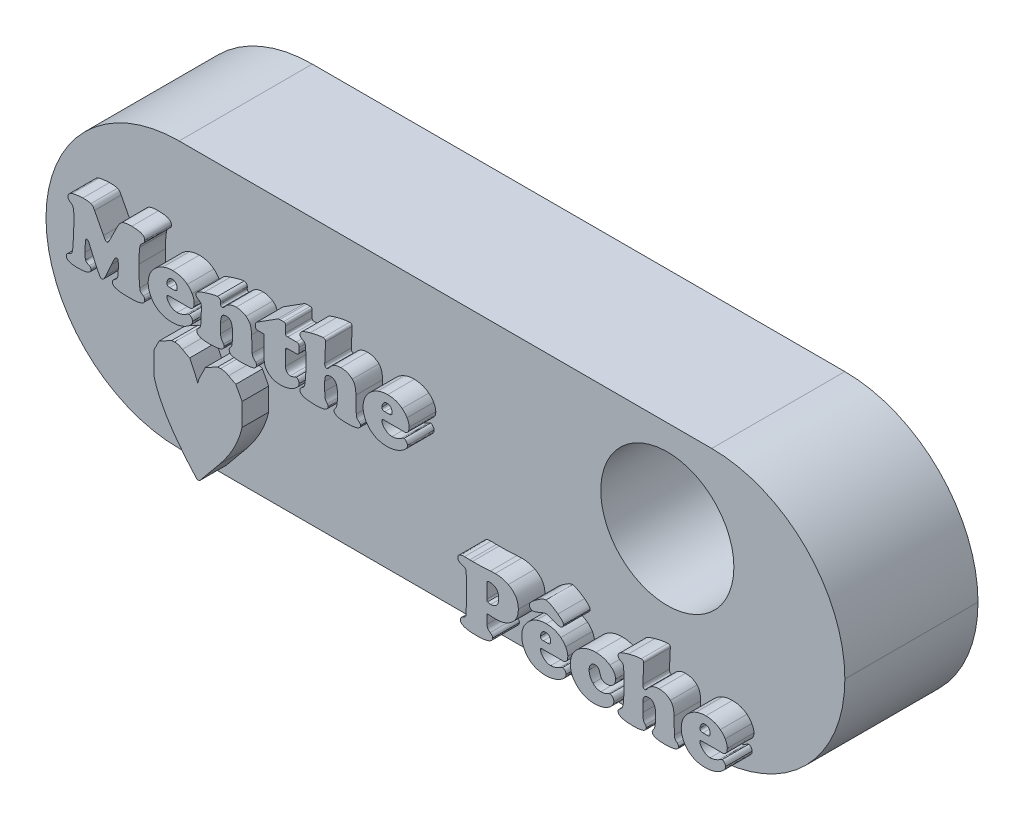
SolidWorks part; units mm, degrees
ref_plane "Plan de face" through (0, 0, 0) normal (0, 0, 1) x (1, 0, 0)
ref_plane "Plan de dessus" through (0, 0, 0) normal (0, 1, 0) x (1, 0, 0)
ref_plane "Plan de droite" through (0, 0, 0) normal (1, 0, 0) x (0, 0, -1)
sketch "Esquisse1" plane through (0, 0, 0) normal (0, 0, 1) x (1, 0, 0)
  line L1 (0, 0) -> (60, 0)
  line L2 (0, 0) -> (0, -20)
  line L3 (0, -20) -> (60, -20)
  line L4 (60, 0) -> (60, -20)
  dimension "D1" = 60
  dimension "D2" = 20
extrude "Boss.-Extru.1" add sketch "Esquisse1" along normal blind 10
fillet "Congé1" radius 10 4 edges at (60, -20, 5) (60, 0, 5) (0, -20, 5) (0, 0, 5)
sketch "Esquisse2" plane through (0, 0, 10) normal (0, 0, 1) x (1, 0, 0)
  text T0 "  Menthe\r\n                   Pêche" font "Cooper Black" height in points 20
extrude "Boss.-Extru.2" add sketch "Esquisse2" along normal blind 2
sketch "Esquisse4" plane through (0, 0, 0) normal (0, 0, 1) x (1, 0, 0)
  circle A0 centre (46.6655, -6.8878) radius 5
extrude "Enlèv. mat.-Extru.1" cut sketch "Esquisse4" along normal blind 10
sketch "Esquisse5" plane through (0, 0, 10) normal (0, 0, 1) x (1, 0, 0)
  text T0 "v" font "SWMap" height 3.5
extrude "Boss.-Extru.3" add sketch "Esquisse5" along normal blind 2
sketch "Esquisse6" plane through (0, 0, 10) normal (0, 0, 1) x (1, 0, 0)
  line L7 (12.4807, -12.1134) -> (11.8849, -11.8026)
  line L8 (10.9667, -12.1048) -> (10.6501, -12.7265)
  line L9 (10.6501, -12.7265) -> (10.6501, -14.1052)
  line L10 (16.1764, -14.2376) -> (16.1764, -12.7524)
  line L11 (16.1764, -12.7524) -> (15.8598, -12.1134)
  line L12 (15.8598, -12.1134) -> (15.2755, -11.8026)
  line L13 (13.6464, -13.9267) -> (13.5054, -14.0707)
  line L14 (12.4807, -12.1134) -> (11.8849, -11.8026)
  line L15 (10.9667, -12.1048) -> (10.6501, -12.7265)
  line L16 (10.6501, -12.7265) -> (10.6501, -14.1052)
  line L17 (16.1764, -14.2376) -> (16.1764, -12.7524)
  line L18 (16.1764, -12.7524) -> (15.8598, -12.1134)
  line L19 (15.8598, -12.1134) -> (15.2755, -11.8026)
  line L20 (13.6464, -13.9267) -> (13.5054, -14.0707)
  spline S14 degree 3 poles (3844.603, 1134.0387) (-9.1292, -38.311) (15.7913, -21.7573) (13.0686, -13.6013) (13.0014, -13.3955) (12.9149, -13.1747) (12.8254, -12.9335) (12.7197, -12.6762) (6.1298, 3.2524) (-24.1776, 9.0682) (3677.1074, 1590.1401) knots -12.728243 -12.728243 -12.728243 -12.728243 0.089256 0.188553 0.297501 0.417109 0.547777 0.687337 0.838518 26.665706 26.665706 26.665706 26.665706 only from (13.1802, -13.9642) to (12.4807, -12.1134)
  spline S15 degree 3 poles (587.959, 3946.2573) (12.648, -51.8598) (17.3042, 25.8245) (0.4195, -47.052) (568.98, 3949.021) knots -54.599144 -54.599144 -54.599144 -54.599144 0.529824 53.467941 53.467941 53.467941 53.467941 only from (11.8849, -11.8026) to (11.7093, -11.7767)
  spline S16 degree 3 poles (-1233.2066, 3789.2515) (37.5147, -63.203) (-8.3641, 47.0449) (23.9946, -79.0662) (-1258.6195, 3780.9629) knots -31.518562 -31.518562 -31.518562 -31.518562 0.435223 35.38032 35.38032 35.38032 35.38032 only from (11.7093, -11.7767) to (11.3323, -11.9091)
  spline S17 degree 3 poles (2009.0822, -3477.0911) (13.6411, 17.2413) (18.4038, -7.9741) (11.1107, -12.0374) (7.9091, -13.694) (-4.7846, 5.7961) (1645.5506, -3662.6786) knots -59.489645 -59.489645 -59.489645 -59.489645 0.354396 0.639968 0.857046 26.377837 26.377837 26.377837 26.377837 only from (11.3323, -11.9091) to (10.9667, -12.1048)
  spline S18 degree 3 poles (-3836.134, -1109.4642) (63.2387, 29.0811) (5.9159, -2.229) (11.0298, -15.3237) (18.91, -31.0876) (80.5387, -15.7714) (-3432.1342, -2050.4369) knots -14.844679 -14.844679 -14.844679 -14.844679 0.226693 0.467185 0.724557 19.777076 19.777076 19.777076 19.777076 only from (10.6501, -14.1052) to (11.7295, -16.5633)
  spline S19 degree 3 poles (-3268.2956, -2305.2844) (4.9825, 15.5644) (3.0038, -4.5004) (11.948, -16.8673) (12.1051, -17.0786) (12.3007, -17.3334) (12.5281, -17.6342) (12.7952, -17.9769) (33.9761, -45.6072) (72.3133, -59.8182) (-3088.6173, -2542.2179) knots -16.179282 -16.179282 -16.179282 -16.179282 0.053217 0.12705 0.222114 0.336151 0.472253 0.62734 0.803045 37.885684 37.885684 37.885684 37.885684 only from (11.7295, -16.5633) to (13.419, -18.7853)
  spline S20 degree 3 poles (3108.5675, -2551.7121) (-37.811, -35.1971) (-0.0046, -36.1208) (13.9989, -18.0518) (14.2513, -17.732) (14.4724, -17.4454) (14.6624, -17.1914) (14.8238, -16.9728) (21.4502, -7.8129) (9.6465, 14.1742) (3307.7145, -2287.4565) knots -24.739508 -24.739508 -24.739508 -24.739508 0.183136 0.349903 0.499297 0.632991 0.749514 0.849515 0.933004 13.230667 13.230667 13.230667 13.230667 only from (13.419, -18.7853) to (15.0683, -16.6266)
  spline S21 degree 3 poles (3430.9793, -2097.2443) (-52.7913, -15.306) (7.6962, -30.9989) (15.77, -15.4208) (21.2981, -2.0665) (-31.8036, 30.3158) (3828.6402, -1223.5898) knots -19.08667 -19.08667 -19.08667 -19.08667 0.27548 0.532761 0.773255 16.618162 16.618162 16.618162 16.618162 only from (15.0683, -16.6266) to (16.1764, -14.2376)
  spline S22 degree 3 poles (644.2769, 3938.291) (14.7565, -51.6748) (21.3639, 27.7582) (3.1353, -50.9536) (627.0794, 3940.8651) knots -50.617147 -50.617147 -50.617147 -50.617147 0.489777 52.311517 52.311517 52.311517 52.311517 only from (15.2755, -11.8026) to (15.1086, -11.7767)
  spline S23 degree 3 poles (-1203.2594, 3797.9802) (40.6365, -63.015) (-4.5108, 46.9654) (26.6781, -79.1301) (-1229.2734, 3789.5071) knots -31.580828 -31.580828 -31.580828 -31.580828 0.433634 35.522114 35.522114 35.522114 35.522114 only from (15.1086, -11.7767) to (14.7229, -11.9091)
  spline S24 degree 3 poles (-1803.9059, 3550.266) (52.9114, -2.5252) (31.2141, -2.5411) (14.4957, -12.0377) (10.845, -13.8855) (-0.8275, 1.8881) (1667.8389, -3653.483) knots -137.313568 -137.313568 -137.313568 -137.313568 0.364348 0.648317 0.864177 29.749606 29.749606 29.749606 29.749606 only from (14.7229, -11.9091) to (14.3545, -12.1048)
  spline S25 degree 3 poles (-3534.0211, 1833.631) (40.3586, -14.9997) (16.2434, -7.9177) (14.2522, -12.3115) (14.1882, -12.475) (14.1067, -12.6813) (14.0086, -12.9299) (13.8996, -13.2237) (5.8362, -35.9895) (-23.9616, -50.8213) (3751.9324, -1435.324) knots -7.190391 -7.190391 -7.190391 -7.190391 0.043456 0.109956 0.200409 0.312725 0.450185 0.610367 0.793303 37.494525 37.494525 37.494525 37.494525 only from (14.3545, -12.1048) to (13.6464, -13.9267)
  spline S26 degree 3 poles (843.9363, -3926.7955) (10.828, 15.7726) (19.9546, -45.548) (2.5294, 19.0599) (832.9813, -3928.9445) knots -60.477404 -60.477404 -60.477404 -60.477404 0.442775 66.294156 66.294156 66.294156 66.294156 only from (13.5054, -14.0707) to (13.419, -14.0879)
  spline S27 degree 3 poles (-1820.1277, -3568.9332) (49.1443, 42.8981) (-17.5601, -73.557) (39.1184, 47.987) (-1835.0835, -3561.1398) knots -30.851382 -30.851382 -30.851382 -30.851382 0.500538 31.829171 31.829171 31.829171 31.829171 only from (13.419, -14.0879) to (13.1802, -13.9642)
  spline S28 degree 3 poles (13.1802, -13.9642) (13.1643, -13.9074) (13.1308, -13.7876) (13.0686, -13.6013) (13.0014, -13.3955) (12.9149, -13.1747) (12.8254, -12.9335) (12.7197, -12.6762) (12.6056, -12.4004) (12.5232, -12.2111) (12.4807, -12.1134) knots 0 0 0 0 0.089256 0.188553 0.297501 0.417109 0.547777 0.687337 0.838518 1 1 1 1
  spline S29 degree 3 poles (11.8849, -11.8026) (11.8544, -11.7946) (11.7968, -11.7797) (11.7373, -11.7776) (11.7093, -11.7767) knots 0 0 0 0 0.529824 1 1 1 1
  spline S30 degree 3 poles (11.7093, -11.7767) (11.6507, -11.7839) (11.5159, -11.8005) (11.3985, -11.8699) (11.3323, -11.9091) knots 0 0 0 0 0.435223 1 1 1 1
  spline S31 degree 3 poles (11.3323, -11.9091) (11.2902, -11.9342) (11.2142, -11.9797) (11.1107, -12.0374) (11.0312, -12.0785) (10.9851, -12.0973) (10.9667, -12.1048) knots 0 0 0 0 0.354396 0.639968 0.857046 1 1 1 1
  spline S32 degree 3 poles (10.6501, -14.1052) (10.6964, -14.3042) (10.7918, -14.7143) (11.0298, -15.3237) (11.3415, -15.9472) (11.5973, -16.3533) (11.7295, -16.5633) knots 0 0 0 0 0.226693 0.467185 0.724557 1 1 1 1
  spline S33 degree 3 poles (11.7295, -16.5633) (11.7582, -16.6036) (11.8269, -16.6998) (11.948, -16.8673) (12.1051, -17.0786) (12.3007, -17.3334) (12.5281, -17.6342) (12.7952, -17.9769) (13.0939, -18.3667) (13.3066, -18.6405) (13.419, -18.7853) knots 0 0 0 0 0.053217 0.12705 0.222114 0.336151 0.472253 0.62734 0.803045 1 1 1 1
  spline S34 degree 3 poles (13.419, -18.7853) (13.5231, -18.6561) (13.7219, -18.4093) (13.9989, -18.0518) (14.2513, -17.732) (14.4724, -17.4454) (14.6624, -17.1914) (14.8238, -16.9728) (14.9568, -16.7889) (15.0339, -16.6766) (15.0683, -16.6266) knots 0 0 0 0 0.183136 0.349903 0.499297 0.632991 0.749514 0.849515 0.933004 1 1 1 1
  spline S35 degree 3 poles (15.0683, -16.6266) (15.2003, -16.4223) (15.4556, -16.0274) (15.77, -15.4208) (16.0151, -14.8288) (16.1237, -14.4308) (16.1764, -14.2376) knots 0 0 0 0 0.27548 0.532761 0.773255 1 1 1 1
  spline S36 degree 3 poles (15.2755, -11.8026) (15.2489, -11.7947) (15.1944, -11.7785) (15.1376, -11.7773) (15.1086, -11.7767) knots 0 0 0 0 0.489777 1 1 1 1
  spline S37 degree 3 poles (15.1086, -11.7767) (15.049, -11.7839) (14.9116, -11.8007) (14.7911, -11.8699) (14.7229, -11.9091) knots 0 0 0 0 0.433634 1 1 1 1
  spline S38 degree 3 poles (14.7229, -11.9091) (14.6788, -11.934) (14.6002, -11.9783) (14.4957, -12.0377) (14.4167, -12.0777) (14.3718, -12.0972) (14.3545, -12.1048) knots 0 0 0 0 0.364348 0.648317 0.864177 1 1 1 1
  spline S39 degree 3 poles (14.3545, -12.1048) (14.3408, -12.1296) (14.3062, -12.1924) (14.2522, -12.3115) (14.1882, -12.475) (14.1067, -12.6813) (14.0086, -12.9299) (13.8996, -13.2237) (13.78, -13.5616) (13.6927, -13.8002) (13.6464, -13.9267) knots 0 0 0 0 0.043456 0.109956 0.200409 0.312725 0.450185 0.610367 0.793303 1 1 1 1
  spline S40 degree 3 poles (13.5054, -14.0707) (13.493, -14.075) (13.4651, -14.0848) (13.4355, -14.0868) (13.419, -14.0879) knots 0 0 0 0 0.442775 1 1 1 1
  spline S41 degree 3 poles (13.419, -14.0879) (13.3713, -14.0824) (13.276, -14.0715) (13.2121, -13.9999) (13.1802, -13.9642) knots 0 0 0 0 0.500538 1 1 1 1
  dimension "D1" = 0
extrude "Boss.-Extru.4" add sketch "Esquisse6" along normal blind 2
